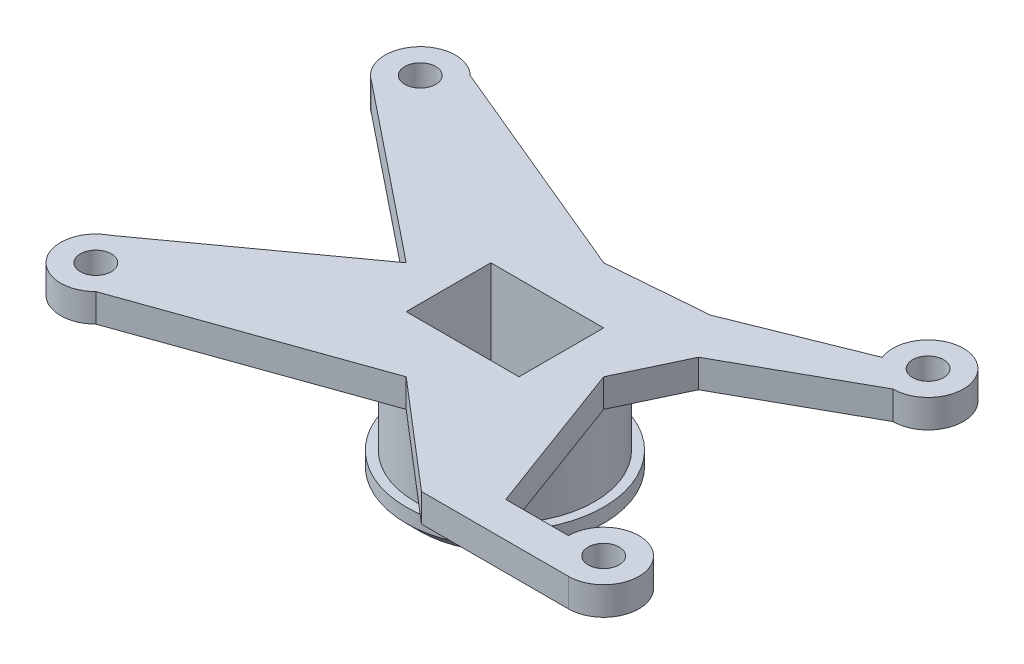
SolidWorks part; units mm, degrees
ref_plane "Front Plane" through (0, 0, 0) normal (0, 0, 1) x (1, 0, 0)
ref_plane "Top Plane" through (0, 0, 0) normal (0, 1, 0) x (1, 0, 0)
ref_plane "Right Plane" through (0, 0, 0) normal (1, 0, 0) x (0, 0, -1)
sketch "Sketch1" plane through (0, 0, 0) normal (0, 1, 0) x (1, 0, 0)
  circle A0 centre (0, 0) radius 6.35
  dimension "D1" = 12.7
extrude "Boss-Extrude1" add sketch "Sketch1" against normal blind 5
sketch "Sketch2" plane through (0, 0, 0) normal (0, 1, 0) x (1, 0, 0)
  circle A0 centre (0, 0) radius 7
  dimension "D1" = 14
extrude "Boss-Extrude2" add sketch "Sketch2" along normal blind 2
extrude "Boss-Extrude3" add sketch "Sketch2<2>" against normal blind 2 from surface starting at face at (0, -5, 6.35)
sketch "Sketch2<2>" plane through (0, 0, 0) normal (0, 1, 0) x (1, 0, 0) same geometry as "Sketch2"
chamfer "Chamfer1" distance 1 angle 45 2 edges at (0, 0, 7) (0, -7, 7)
sketch "Sketch3" plane through (0, -7, 0) normal (0, -1, 0) x (1, 0, 0)
  line L1 (-4, -3) -> (4, -3)
  line L2 (-4, -3) -> (-4, 3)
  line L3 (-4, 3) -> (4, 3)
  line L4 (4, -3) -> (4, 3)
  line L5 (-4, -3) -> (4, 3) construction
  line L6 (-4, 3) -> (4, -3) construction
  point P0 (0, 0)
  dimension "D1" = 8
  dimension "D2" = 6
extrude "Cut-Extrude1" cut sketch "Sketch3" against normal through all
sketch "Sketch4" plane through (0, 2, 0) normal (0, 1, 0) x (1, 0, 0)
  line L0 (0, 0) -> (0, 14.5) construction
  line L1 (0, 0) -> (20.3185, 0) construction
  line L2 (20.5, 14.5) -> (-20.5, 14.5)
  line L3 (-20.5, 14.5) -> (-20.5, -13.5)
  line L4 (-20.5, -13.5) -> (20.5, -13.5)
  line L5 (20.5, -13.5) -> (20.5, 14.5)
  circle A0 centre (-18, 12) radius 1.1
  circle A1 centre (-18, -11) radius 1.1
  circle A2 centre (18, -11) radius 1.1
  circle A3 centre (18, 12) radius 1.1
  point P9 (0, 14.5)
  dimension "D4" = 36
  dimension "D5" = 2.2
  dimension "D6" = 23
  dimension "D7" = 2.5
  dimension "D8" = 2.5
  dimension "D1" = 41
  dimension "D2" = 28
  dimension "D3" = 14.5
sketch "Sketch6" plane through (0, 2, 0) normal (0, 1, 0) x (1, 0, 0)
  circle A0 centre (-18, 12) radius 1.1
  circle A1 centre (18, 12) radius 1.1
  circle A2 centre (18, -11) radius 1.1
  circle A3 centre (-18, -11) radius 1.1
  circle A4 centre (-18, -11) radius 2.5
  circle A5 centre (18, -11) radius 2.5
  circle A6 centre (18, 12) radius 2.5
  circle A7 centre (-18, 12) radius 2.5
  dimension "D1" = 5
  dimension "D2" = 2.2
extrude "Boss-Extrude4" add sketch "Sketch6" along normal blind 1 and the other way blind 1 separate body
sketch "Sketch8" plane through (0, 3, 0) normal (0, 1, 0) x (1, 0, 0)
  line L0 (111.2976, -88.9946) -> (-372.7024, -88.9946) construction
sketch "Sketch7" plane through (0, 3, 0) normal (0, 1, 0) x (1, 0, 0)
  line L3 (-19.7678, 10.2322) -> (-16.2322, 10.2322)
  line L7 (-16.2322, 10.2322) -> (-16.2322, 13.7678)
  line L27 (15.5, -11) -> (11.058, -11)
  line L28 (-4, -3) -> (4, -3)
  line L29 (-4, -3) -> (-4, 3)
  line L30 (-4, 3) -> (4, 3)
  line L31 (4, -3) -> (4, 3)
  line L32 (-4, -3) -> (4, 3) construction
  line L33 (-4, 3) -> (4, -3) construction
  line L34 (11.058, -11) -> (7, 0)
  line L35 (0, 0) -> (20.3185, 0) construction
  line L36 (18, -13.5) -> (7.583, -13.5)
  line L37 (-20.5, -13.5) -> (20.5, -13.5) construction
  line L38 (7.583, -13.5) -> (0, -7)
  line L39 (-19.7678, -9.2322) -> (-16.2322, -9.2322)
  line L40 (-16.2322, -12.7678) -> (0, -7)
  line L41 (-19.7678, -9.2322) -> (-7, 0)
  line L42 (-19.7678, 10.2322) -> (-7, 0)
  line L43 (-16.2322, -9.2322) -> (-16.2322, -12.7678)
  line L44 (-16.2322, 13.7678) -> (0, 7)
  line L45 (0, 0) -> (0, 14.5) construction
  line L46 (0, 7) -> (7, 7.5722)
  line L48 (7, 0) -> (9.1598, 4.5634)
  line L51 (15.5, -11) -> (18, -13.5)
  line L52 (7, 7.5722) -> (15.6808, 11.0665)
  line L53 (15.6808, 11.0665) -> (18, 9.5)
  line L54 (18, 9.5) -> (9.1598, 4.5634)
  circle A0 centre (18, 12) radius 2.5 construction
  circle A5 centre (18, -11) radius 2.5 construction
  circle A6 centre (0, 0) radius 7 construction
  circle A7 centre (-18, -11) radius 2.5 construction
  circle A8 centre (-18, 12) radius 2.5 construction
  point P34 (0, 0)
  dimension "D2" = 60
extrude "Boss-Extrude5" add sketch "Sketch7" against normal up to surface (2 mm away) up to face at (-18, 1, -10.9)
